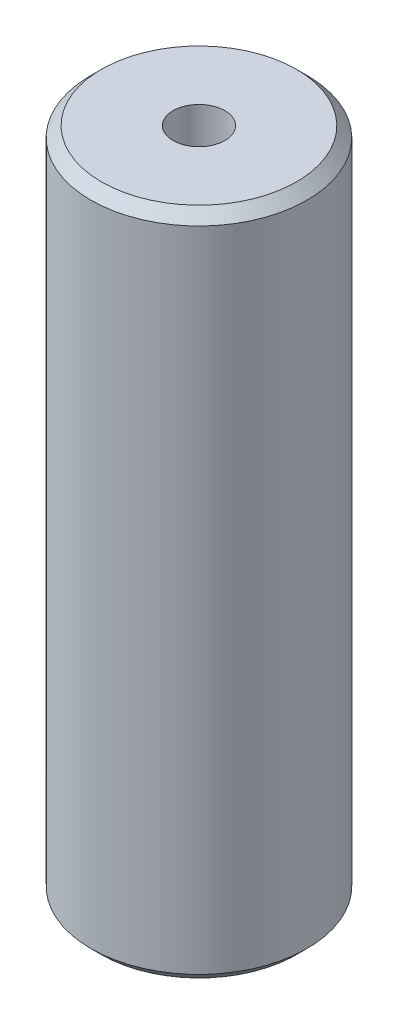
SolidWorks part; units mm, degrees
ref_plane "Front Plane" through (0, 0, 0) normal (0, 0, 1) x (1, 0, 0)
ref_plane "Top Plane" through (0, 0, 0) normal (0, 1, 0) x (1, 0, 0)
ref_plane "Right Plane" through (0, 0, 0) normal (1, 0, 0) x (0, 0, -1)
sketch "Sketch1" plane through (0, 0, 0) normal (0, 1, 0) x (1, 0, 0)
  circle A0 centre (0, 0) radius 7.5
  dimension "SHAFT_OD" = 15
extrude "Boss-Extrude1" add sketch "Sketch1" along normal blind 46.4444
sketch "Sketch2" plane through (0, 0, 0) normal (0, 1, 0) x (1, 0, 0)
  circle A0 centre (0, 0) radius 1.7995
  dimension "BORE_D" = 3.599
extrude "Cut-Extrude1" cut sketch "Sketch2" along normal through all
chamfer "Chamfer1" distance 0.7329 angle 45 2 edges at (0, 46.4444, 7.5) (0, 0, 7.5)
